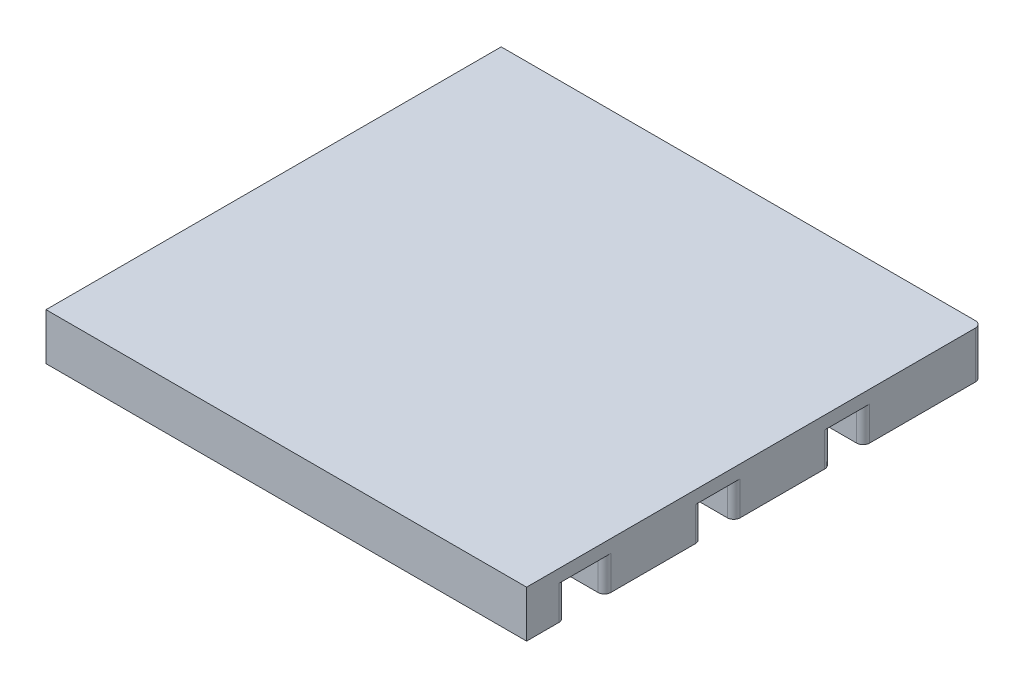
SolidWorks part; units mm, degrees
ref_plane "Front Plane" through (0, 0, 0) normal (0, 0, 1) x (1, 0, 0)
ref_plane "Top Plane" through (0, 0, 0) normal (0, 1, 0) x (1, 0, 0)
ref_plane "Right Plane" through (0, 0, 0) normal (1, 0, 0) x (0, 0, -1)
sketch "Sketch3" plane through (0, 0, 0) normal (0, 1, 0) x (1, 0, 0)
  line L1 (0, 0) -> (149, 0)
  line L2 (0, 0) -> (0, -141.12)
  line L3 (0, -141.12) -> (149, -141.12)
  line L4 (149, 0) -> (149, -141.12)
  dimension "D1" = 141.12
  dimension "D2" = 149
extrude "Boss-Extrude1" add sketch "Sketch3" along normal blind 4
sketch "Sketch5" plane through (0, 4, 0) normal (0, 1, 0) x (1, 0, 0)
  line L0 (0, 0) -> (0, -141.12) construction
  line L1 (149, 0) -> (82, 0)
  line L2 (149, 0) -> (149, -36.8)
  line L3 (149, -36.8) -> (82, -36.8)
  line L4 (82, 0) -> (82, -36.8)
  line L5 (0, -9.9) -> (67, -9.9)
  line L6 (0, -9.9) -> (0, -40.1)
  line L7 (0, -40.1) -> (67, -40.1)
  line L8 (67, -9.9) -> (67, -40.1)
  line L9 (149, 0) -> (0, 0) construction
  line L10 (149, -141.12) -> (149, 0) construction
  line L11 (0, -50) -> (67, -50)
  line L12 (0, -50) -> (0, -80.2)
  line L13 (0, -80.2) -> (67, -80.2)
  line L14 (67, -50) -> (67, -80.2)
  line L15 (0, -90.1) -> (67, -90.1)
  line L16 (0, -90.1) -> (0, -120.3)
  line L17 (0, -120.3) -> (67, -120.3)
  line L18 (67, -90.1) -> (67, -120.3)
  line L19 (149, -46.7) -> (82, -46.7)
  line L20 (149, -46.7) -> (149, -76.9)
  line L21 (149, -76.9) -> (82, -76.9)
  line L22 (82, -46.7) -> (82, -76.9)
  line L23 (12.85, -9.9) -> (12.85, -23.7) construction
  line L24 (149, -86.8) -> (82, -86.8)
  line L25 (149, -86.8) -> (149, -117)
  line L26 (149, -117) -> (82, -117)
  line L27 (82, -86.8) -> (82, -117)
  line L28 (12.85, -23.7) -> (12.85, -28.3) construction
  line L29 (12.85, -28.3) -> (12.85, -40.1) construction
  line L30 (12.85, -23.7) -> (40.15, -23.7)
  line L31 (12.85, -28.3) -> (40.15, -28.3)
  line L32 (12.85, -50) -> (12.85, -63.8) construction
  line L33 (12.85, -63.8) -> (12.85, -68.4) construction
  line L34 (12.85, -68.4) -> (12.85, -80.2) construction
  line L35 (12.85, -63.8) -> (40.15, -63.8)
  line L36 (12.85, -68.4) -> (40.15, -68.4)
  line L37 (97.3, -36.8) -> (97.3, -25) construction
  line L38 (97.3, -25) -> (97.3, -20.4) construction
  line L39 (97.3, -20.4) -> (97.3, 0) construction
  line L40 (97.3, -20.4) -> (124.6, -20.4)
  line L41 (97.3, -25) -> (124.6, -25)
  line L42 (97.3, -46.7) -> (97.3, -60.5) construction
  line L43 (97.3, -60.5) -> (97.3, -65.1) construction
  line L44 (97.3, -65.1) -> (97.3, -76.9) construction
  line L45 (97.3, -60.5) -> (124.6, -60.5)
  line L46 (97.3, -65.1) -> (124.6, -65.1)
  line L47 (12.85, -90.1) -> (12.85, -103.9) construction
  line L48 (12.85, -103.9) -> (12.85, -108.5) construction
  line L49 (12.85, -108.5) -> (12.85, -120.3) construction
  line L50 (12.85, -103.9) -> (40.15, -103.9)
  line L51 (12.85, -108.5) -> (40.15, -108.5)
  line L52 (97.3, -86.8) -> (97.3, -100.6) construction
  line L53 (97.3, -100.6) -> (97.3, -105.2) construction
  line L54 (97.3, -105.2) -> (97.3, -117) construction
  line L55 (97.3, -100.6) -> (124.6, -100.6)
  line L56 (97.3, -105.2) -> (124.6, -105.2)
  arc A0 (12.85, -28.3) -> (12.85, -23.7) centre (12.85, -26) cw
  arc A1 (40.15, -23.7) -> (40.15, -28.3) centre (40.15, -26) cw
  arc A2 (12.85, -63.8) -> (12.85, -68.4) centre (12.85, -66.1) ccw
  arc A3 (40.15, -63.8) -> (40.15, -68.4) centre (40.15, -66.1) cw
  arc A4 (97.3, -25) -> (97.3, -20.4) centre (97.3, -22.7) cw
  arc A5 (124.6, -20.4) -> (124.6, -25) centre (124.6, -22.7) cw
  arc A6 (97.3, -65.1) -> (97.3, -60.5) centre (97.3, -62.8) cw
  arc A7 (124.6, -60.5) -> (124.6, -65.1) centre (124.6, -62.8) cw
  arc A8 (12.85, -103.9) -> (12.85, -108.5) centre (12.85, -106.2) ccw
  arc A9 (40.15, -103.9) -> (40.15, -108.5) centre (40.15, -106.2) cw
  arc A10 (97.3, -100.6) -> (97.3, -105.2) centre (97.3, -102.9) ccw
  arc A11 (124.6, -100.6) -> (124.6, -105.2) centre (124.6, -102.9) cw
  line M18 (0, 0) -> (0, -141.12)
  line M20 (149, -141.12) -> (149, 0)
  line M21 (149, 0) -> (0, 0)
  dimension "D1" = 67
  dimension "D2" = 36.8
  dimension "D3" = 67
  dimension "D4" = 30.2
  dimension "D5" = 9.9
  dimension "D6" = 30.2
  dimension "D7" = 9.9
  dimension "D8" = 9.9
  dimension "D9" = 30.2
  dimension "D10" = 9.9
  dimension "D11" = 30.2
  dimension "D12" = 9.9
  dimension "D13" = 30.2
  dimension "D14" = 67
  dimension "D15" = 67
  dimension "D16" = 67
  dimension "D17" = 67
  dimension "D18" = 13.8
  dimension "D19" = 11.8
  dimension "D20" = 12.85
  dimension "D21" = 27.3
  dimension "D22" = 13.8
  dimension "D23" = 11.8
  dimension "D24" = 27.3
  dimension "D25" = 4.6
  dimension "D26" = 11.8
  dimension "D27" = 24.4
  dimension "D28" = 27.3
  dimension "D29" = 11.8
  dimension "D30" = 13.8
  dimension "D31" = 13.8
  dimension "D32" = 11.8
  dimension "D33" = 13.8
  dimension "D34" = 11.8
extrude "Boss-Extrude2" add sketch "Sketch5" against normal blind 14.5 contours L8 L5 L7 L30 A1 L31 A0 M18 | L4 L3 L40 A5 L41 A4 M21 M20 | L14 L11 L13 L35 A3 L36 A2 M18 | L19 L22 L21 L45 A7 L46 A6 M20 | L18 L15 L17 L50 A9 L51 A8 M18 | L24 L27 L26 L55 A11 L56 A10 M20 region at (115.7785, 4, 18.1368) region at (148.2651, 4, 101.9) region at (148.2651, 4, 61.8) region at (33.5, 4, 90.8349) region at (33.5, 4, 50.7349) region at (33.5, 4, 10.6349)
fillet "Fillet1" radius 2 24 edges at (149, -5.25, 86.8) (149, -5.25, 117) (82, -5.25, 117) (82, -5.25, 86.8) (67, -5.25, 90.1) (67, -5.25, 120.3) (0, -5.25, 120.3) (0, -5.25, 90.1) (0, -5.25, 80.2) (82, -5.25, 76.9) (149, -5.25, 76.9) (149, -5.25, 46.7) (82, -5.25, 46.7) (67, -5.25, 50) (67, -5.25, 80.2) (0, -5.25, 50) (0, -5.25, 40.1) (67, -5.25, 40.1) (82, -5.25, 36.8) (149, -5.25, 36.8) (149, -3.25, 0) (82, -5.25, 0) (67, -5.25, 9.9) (0, -5.25, 9.9)
sketch "Sketch6" plane through (0, 0, 0) normal (0, -1, 0) x (1, 0, 0)
  line L0 (0, 129.12) -> (149, 129.12)
  line L1 (0, 118.3) -> (0, 141.12) construction
  line L2 (149, 141.12) -> (149, 115) construction
  line L3 (149, 129.12) -> (149, 141.12)
  line L4 (149, 141.12) -> (0, 141.12)
  line L5 (0, 141.12) -> (0, 129.12)
  dimension "D1" = 12
extrude "Boss-Extrude3" add sketch "Sketch6" along normal blind 10.5
fillet "Fillet2" radius 2 2 edges at (149, -5.25, 129.12) (0, -5.25, 129.12)
